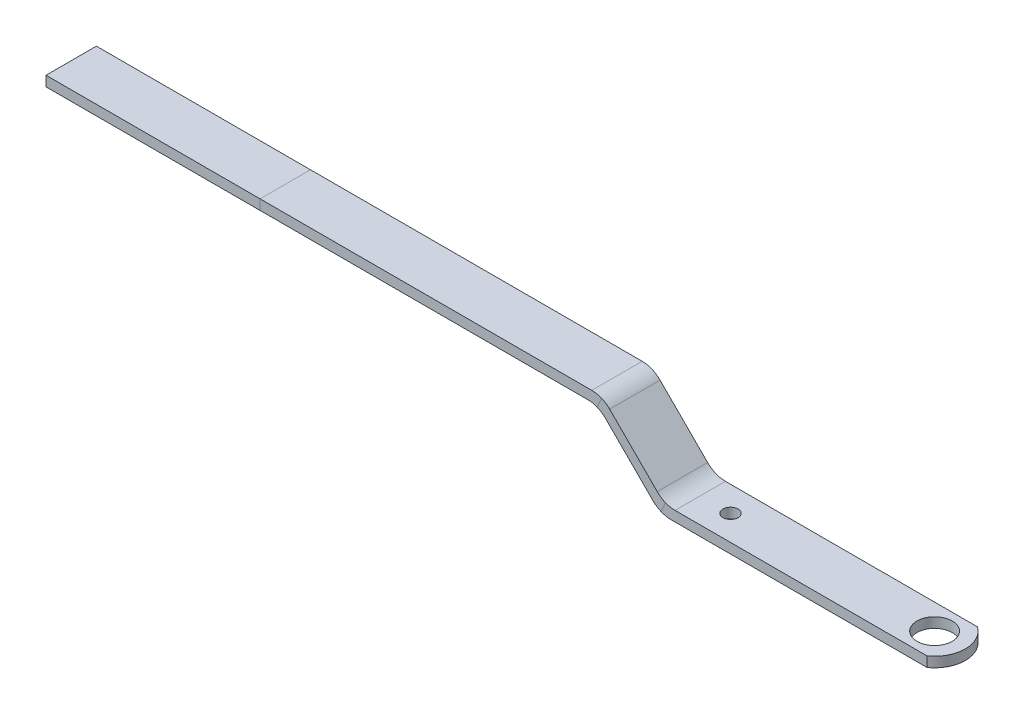
SolidWorks part; units mm, degrees
ref_plane "Front Plane" through (0, 0, 0) normal (0, 0, 1) x (1, 0, 0)
ref_plane "Top Plane" through (0, 0, 0) normal (0, 1, 0) x (1, 0, 0)
ref_plane "Right Plane" through (0, 0, 0) normal (1, 0, 0) x (0, 0, -1)
sketch "Sketch2" plane through (0, 0, 0) normal (0, 0, 1) x (1, 0, 0)
  line L0 (0, 0) -> (105, 0)
  line L1 (0, 0) -> (-24.7487, 24.7487)
  line L2 (-24.7487, 24.7487) -> (-159.7487, 24.7487)
  line L3 (-159.7487, 24.7487) -> (-244.7487, 24.7487)
  dimension "D1" = 135
  dimension "D2" = 105
  dimension "D3" = 135
  dimension "D4" = 85
  dimension "D5" = 35
ref_plane "Plane1" through (105, 0, 0) normal (1, 0, 0) x (0, 0, -1)
sketch "Sketch3" plane through (105, 0, 0) normal (1, 0, 0) x (0, 0, -1)
  line L1 (-10, -2) -> (10, -2)
  line L2 (-10, -2) -> (-10, 2)
  line L3 (-10, 2) -> (10, 2)
  line L4 (10, -2) -> (10, 2)
  line L5 (-10, -2) -> (10, 2) construction
  line L6 (-10, 2) -> (10, -2) construction
  point P0 (0, 0)
  dimension "D1" = 20
  dimension "D2" = 4
sweep "Sweep1" add profiles "Sketch3" path "Sketch2"
fillet "Fillet1" radius 10 4 edges at (0.8284, 2, 0) (-23.9203, 26.7487, 0) (-0.8284, -2, 0) (-25.5772, 22.7487, 0)
sketch "Sketch4" plane through (0, 2, 0) normal (0, 1, 0) x (1, 0, 0)
  line L0 (0, 0) -> (105, 0) construction
  line L1 (105, -10) -> (4.9706, -10) construction
  line L2 (105, -11) -> (105, 11) construction
  line L3 (105, 10) -> (105, -10) construction
  line L4 (105, 10) -> (105, -10)
  circle A0 centre (98, 0) radius 7
  circle A1 centre (17, 0) radius 3
  arc A2 (105, -10) -> (105, 10) centre (98, 0) ccw
  line M6 (105, -10) -> (105, 10)
  dimension "D1" = 6
  dimension "D2" = 14
  dimension "D4" = 7
  dimension "D3" = 81
extrude "Boss-Extrude1" add sketch "Sketch4" against normal blind 4 contours A2 L4 M6 region at (107.1261, 2, 0)
extrude "Cut-Extrude6" cut sketch "Sketch4<4>" against normal blind 4 contours A0 | A1 region at (98, 2, 0) region at (17, 2, 0)
sketch "Sketch4<4>" plane through (0, 2, 0) normal (0, 1, 0) x (1, 0, 0) same geometry as "Sketch4"
sketch "Sketch5" plane through (0, 22.7487, 0) normal (0, -1, 0) x (1, 0, 0)
  line L0 (-159.7487, 0) -> (-244.7487, 0) construction
  line L1 (-159.7487, 10) -> (-159.7487, -10) construction
  circle A0 centre (-175.7487, 0) radius 4
  dimension "D1" = 8
  dimension "D2" = 16
extrude "Boss-Extrude2" add sketch "Sketch5" along normal blind 2
fillet "Fillet4" radius 2 1 edges at (-171.7487, 20.7487, 0) type face fillet first side face at (-171.7487, 20.7487, 0) second side face at (-171.7487, 20.7487, 0)
